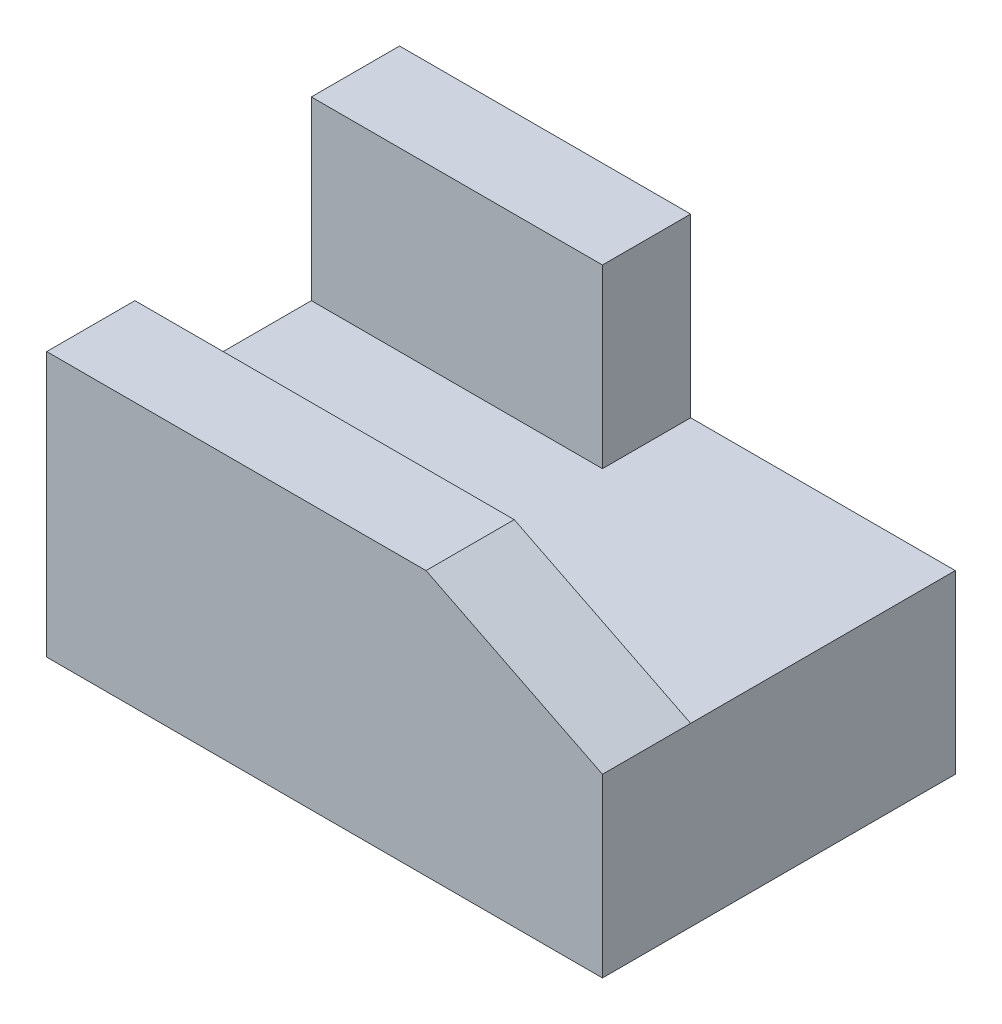
SolidWorks part; units mm, degrees
note: The reader was unsure of these and kept them because the rebuilt part matched: shared geometry of "Sketch1<3>", "Sketch1<4>".
ref_plane "Front Plane" through (0, 0, 0) normal (0, 0, 1) x (1, 0, 0)
ref_plane "Top Plane" through (0, 0, 0) normal (0, 1, 0) x (1, 0, 0)
ref_plane "Right Plane" through (0, 0, 0) normal (1, 0, 0) x (0, 0, -1)
sketch "Sketch1" plane through (0, 0, 0) normal (0, 1, 0) x (1, 0, 0)
  line L0 (0, 30) -> (33, 30)
  line L1 (0, 0) -> (63, 0)
  line L2 (0, 0) -> (0, 40)
  line L3 (0, 40) -> (63, 40)
  line L4 (63, 0) -> (63, 40)
  line L5 (33, 30) -> (33, 40)
  line L6 (0, 10) -> (63, 10)
  dimension "D1" = 40
  dimension "D2" = 63
  dimension "D3" = 33
  dimension "D4" = 10
  dimension "D5" = 10
extrude "Boss-Extrude1" add sketch "Sketch1" along normal blind 20 contours L2 L6 L4 L3 L5 L0
extrude "Boss-Extrude2" add sketch "Sketch1<3>" along normal blind 30 contours L6 L2 L1 L4
sketch "Sketch1<3>" plane through (0, 0, 0) normal (0, 1, 0) x (1, 0, 0) same geometry as "Sketch1"
extrude "Boss-Extrude3" add sketch "Sketch1<4>" along normal blind 40 contours L0 L5 L3 L2
sketch "Sketch1<4>" plane through (0, 0, 0) normal (0, 1, 0) x (1, 0, 0) same geometry as "Sketch1"
sketch "Sketch2" plane through (0, 0, -10) normal (0, 0, -1) x (-1, 0, 0)
  line L0 (-63, 20) -> (-43, 30)
  line L1 (0, 30) -> (-63, 30) construction
  line L2 (-63, 30) -> (-63, 20) construction
  dimension "D1" = 20
extrude "Cut-Extrude1" cut sketch "Sketch2" against normal blind 10 and the other way through all
